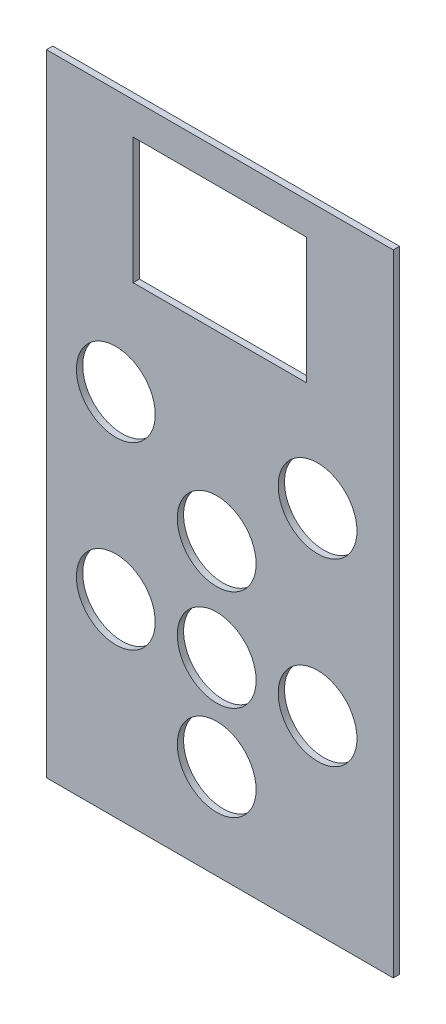
SolidWorks part; units mm, degrees
ref_plane "前视基准面" through (0, 0, 0) normal (0, 0, 1) x (1, 0, 0)
ref_plane "上视基准面" through (0, 0, 0) normal (0, 1, 0) x (1, 0, 0)
ref_plane "右视基准面" through (0, 0, 0) normal (1, 0, 0) x (0, 0, -1)
sketch "草图1" plane through (0, 0, 0) normal (0, 0, 1) x (1, 0, 0)
  line L0 (51.6682, -2.0844) -> (24.1682, -2.0844)
  line L1 (10.4182, 3.0485) -> (65.4182, 3.0485)
  line L2 (10.4182, 3.0485) -> (10.4182, -96.9515)
  line L3 (10.4182, -96.9515) -> (65.4182, -96.9515)
  line L4 (65.4182, 3.0485) -> (65.4182, -96.9515)
  line L5 (51.6682, -2.0844) -> (51.6682, -22.0844)
  line L6 (51.6682, -22.0844) -> (24.1682, -22.0844)
  line L7 (24.1682, -2.0844) -> (24.1682, -22.0844)
  circle A0 centre (37.4182, -81.9515) radius 6.25
  circle A1 centre (37.4182, -66.9515) radius 6.25
  circle A2 centre (21.4182, -66.9515) radius 6.25
  circle A3 centre (53.4182, -66.9515) radius 6.25
  circle A4 centre (37.4182, -50.9515) radius 6.25
  circle A5 centre (53.4182, -38.4515) radius 6.25
  circle A6 centre (21.4182, -38.4515) radius 6.25
  dimension "D3" = 12.5
  dimension "D4" = 12.5
  dimension "D5" = 12.5
  dimension "D6" = 12.5
  dimension "D7" = 12.5
  dimension "D8" = 12.5
  dimension "D9" = 12.5
  dimension "D18" = 27.5
  dimension "D1" = 55
  dimension "D2" = 100
  dimension "D10" = 15
  dimension "D11" = 16
  dimension "D12" = 16
  dimension "D13" = 16
  dimension "D14" = 28.5
  dimension "D15" = 28.5
  dimension "D16" = 27
  dimension "D17" = 15
  dimension "D19" = 20
  dimension "D20" = 13.75
extrude "凸台-拉伸1" add sketch "草图1" along normal blind 1
